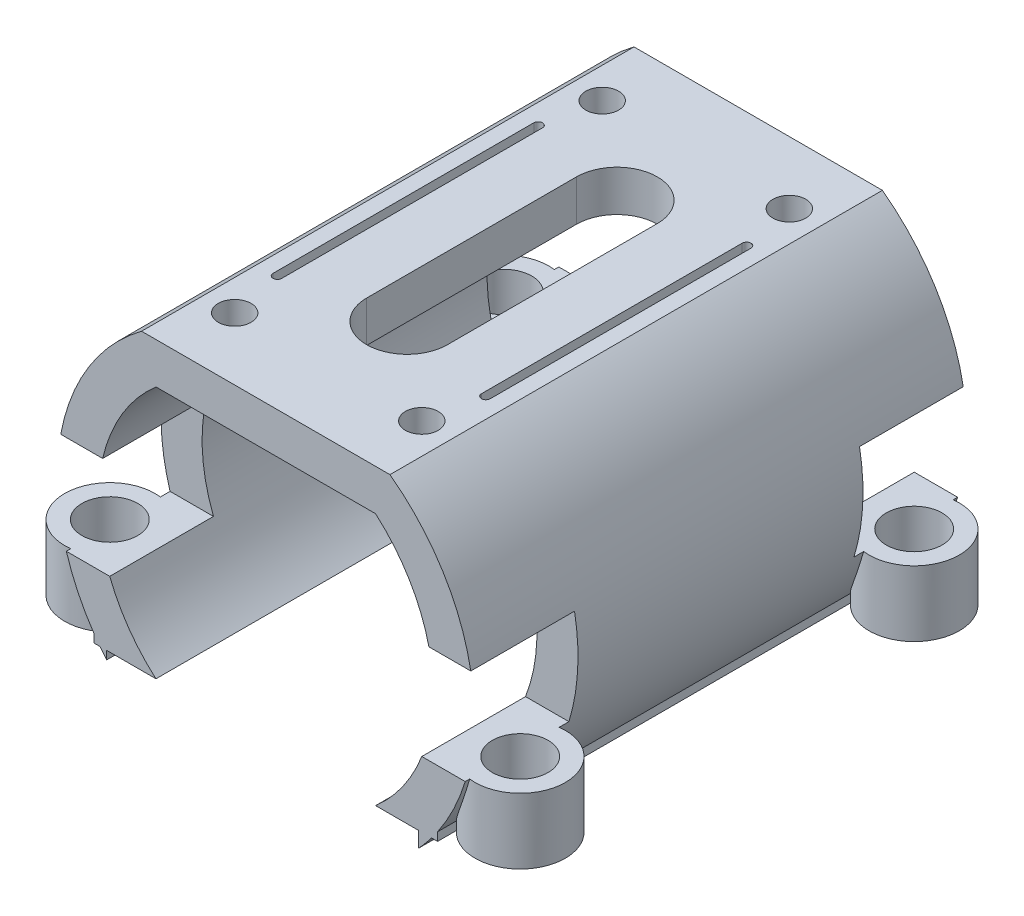
SolidWorks part; units mm, degrees
ref_plane "Alzado" through (0, 0, 0) normal (0, 0, 1) x (1, 0, 0)
ref_plane "Planta" through (0, 0, 0) normal (0, 1, 0) x (1, 0, 0)
ref_plane "Vista lateral" through (0, 0, 0) normal (1, 0, 0) x (0, 0, -1)
sketch "Croquis1" plane through (0, 0, 0) normal (0, 0, 1) x (1, 0, 0)
  line L0 (-6.6895, 7.7) -> (6.6895, 7.7)
  line L1 (-6.6895, -7.7) -> (6.6895, -7.7)
  arc A0 (-6.6895, 7.7) -> (-6.6895, -7.7) centre (0, 0) ccw
  arc A1 (6.6895, -7.7) -> (6.6895, 7.7) centre (0, 0) ccw
  dimension "D1" = 20.4
  dimension "D2" = 7.7
  dimension "D3" = 15.4
extrude "Saliente-Extruir1" add sketch "Croquis1" along normal blind 30
shell "Vaciado1" thickness 2.5 removed face at (0, 0, 30) outward yes
sketch "Croquis2" plane through (0, 0, -2.5) normal (0, 0, -1) x (-1, 0, 0)
  line L1 (-20.823, 15.7006) -> (20.823, 15.7006)
  line L2 (-20.823, 15.7006) -> (-20.823, -15.7006)
  line L3 (-20.823, -15.7006) -> (20.823, -15.7006)
  line L4 (20.823, 15.7006) -> (20.823, -15.7006)
  line L5 (-20.823, 15.7006) -> (20.823, -15.7006) construction
  line L6 (-20.823, -15.7006) -> (20.823, 15.7006) construction
  point P0 (0, 0)
extrude "Cortar-Extruir1" cut sketch "Croquis2" against normal blind 2.5
sketch "Croquis3" plane through (0, 0, 30) normal (0, 0, 1) x (1, 0, 0)
  line L1 (9.3098, -7.7) -> (-9.6926, -7.7)
  line L2 (9.3098, -7.7) -> (9.3098, -10.6722)
  line L3 (9.3098, -10.6722) -> (-9.6926, -10.6722)
  line L4 (-9.6926, -7.7) -> (-9.6926, -10.6722)
extrude "Cortar-Extruir2" cut sketch "Croquis3" against normal blind 48.3
sketch "Croquis4" plane through (0, -7.7, 0) normal (0, -1, 0) x (1, 0, 0)
  line L0 (0, 0) -> (0, 30) construction
  line L1 (6.6895, 30) -> (-6.6895, 30) construction
  line L2 (0, 15) -> (16.7401, 15) construction
  circle A0 centre (12.5, 3) radius 1.7
  circle A1 centre (12.5, 27) radius 1.7
  circle A2 centre (-12.5, 27) radius 1.7
  circle A3 centre (-12.5, 3) radius 1.7
  circle A4 centre (12.5, 3) radius 2.75
  circle A5 centre (12.5, 27) radius 2.75
  circle A6 centre (-12.5, 27) radius 2.75
  circle A7 centre (-12.5, 3) radius 2.75
  dimension "D3" = 3.4
  dimension "D4" = 5.5
  dimension "D1" = 12.5
  dimension "D2" = 12
extrude "Saliente-Extruir2" add sketch "Croquis4" against normal blind 4 separate body
sketch "Croquis5" plane through (0, -7.7, 0) normal (0, -1, 0) x (1, 0, 0)
  line L0 (-7.5664, 30) -> (-12.7, 30) construction
  line L1 (-8.4065, 0.1) -> (-10.4676, 0.1)
  line L2 (-8.4065, 0.1) -> (-8.4065, 30)
  line L3 (-8.4065, 30) -> (-10.4676, 30)
  line L4 (-10.4676, 0.1) -> (-10.4676, 30)
  line L5 (0, 0) -> (0, 12.3583) construction
  line L6 (10.4676, 0.1) -> (10.4676, 30)
  line L7 (8.4065, 30) -> (10.4676, 30)
  line L8 (8.4065, 0.1) -> (8.4065, 30)
  line L9 (8.4065, 0.1) -> (10.4676, 0.1)
extrude "Saliente-Extruir3" add sketch "Croquis5" against normal blind 1.5
sketch "Croquis6" plane through (0, 10.2, 0) normal (0, 1, 0) x (1, 0, 0)
  line L0 (0, 0) -> (0, -30) construction
  line L1 (7.5664, -30) -> (-7.5664, -30) construction
  line L2 (0, -30) -> (0, -15) construction
  line L3 (0, -15) -> (12.7, -15) construction
  line L4 (12.7, -30) -> (12.7, 0) construction
  line L5 (0, -21.3925) -> (0, -8.6075) construction
  line L6 (-2.4626, -21.3925) -> (-2.4626, -8.6075)
  line L7 (2.4626, -21.3925) -> (2.4626, -8.6075)
  line L8 (6.35, -7.0579) -> (6.35, -22.9421) construction
  line L9 (6.6165, -7.0579) -> (6.6165, -22.9421)
  line L10 (6.0835, -7.0579) -> (6.0835, -22.9421)
  line L11 (-6.35, -7.0579) -> (-6.35, -22.9421) construction
  line L12 (-6.6165, -7.0579) -> (-6.6165, -22.9421)
  line L13 (-6.0835, -7.0579) -> (-6.0835, -22.9421)
  arc A0 (-2.4626, -21.3925) -> (2.4626, -21.3925) centre (0, -21.3925) ccw
  arc A1 (2.4626, -8.6075) -> (-2.4626, -8.6075) centre (0, -8.6075) ccw
  arc A2 (6.6165, -7.0579) -> (6.0835, -7.0579) centre (6.35, -7.0579) ccw
  arc A3 (6.0835, -22.9421) -> (6.6165, -22.9421) centre (6.35, -22.9421) ccw
  circle A4 centre (5.7, -3.805) radius 1
  circle A5 centre (5.7, -26.195) radius 1
  arc A6 (-6.6165, -7.0579) -> (-6.0835, -7.0579) centre (-6.35, -7.0579) cw
  arc A7 (-6.0835, -22.9421) -> (-6.6165, -22.9421) centre (-6.35, -22.9421) cw
  circle A8 centre (-5.7, -3.805) radius 1
  circle A9 centre (-5.7, -26.195) radius 1
  point P11 (0, -15)
  point P17 (6.35, -15)
  point P29 (-6.35, -15)
  point P34 (0, -8.6075)
  dimension "D1" = 2
extrude "Cortar-Extruir3" cut sketch "Croquis6" against normal blind 7
sketch "Croquis9" plane through (0, 0, 0) normal (1, 0, 0) x (0, 0, -1)
  line L0 (-15, -7.7) -> (-15, 10.2) construction
  line L1 (-25.1474, -7.7) -> (-4.8526, -7.7) construction
  line L2 (-30, 10.2) -> (0, 10.2) construction
  line L3 (-30, -3.7) -> (0, -3.7) construction
  line L4 (1.4369, -3.7) -> (-6.3186, -3.7)
  line L5 (1.4369, -3.7) -> (1.4369, 2.3004)
  line L6 (1.4369, 2.3004) -> (-6.3186, 2.3004)
  line L7 (-6.3186, -3.7) -> (-6.3186, 2.3004)
  line L8 (-31.4369, 2.3004) -> (-23.6814, 2.3004)
  line L9 (-23.6814, -3.7) -> (-23.6814, 2.3004)
  line L10 (-31.4369, -3.7) -> (-23.6814, -3.7)
  line L11 (-31.4369, -3.7) -> (-31.4369, 2.3004)
extrude "Cortar-Extruir4" cut sketch "Croquis9" against normal blind 32 and the other way blind 30
sketch "Croquis10" plane through (0, -7.7, 0) normal (0, -1, 0) x (1, 0, 0)
  circle A0 centre (12.5, 27) radius 1.7
  circle A1 centre (-12.5, 27) radius 1.7
  circle A2 centre (12.5, 3) radius 1.7
  circle A3 centre (-12.5, 3) radius 1.7
extrude "Cortar-Extruir5" cut sketch "Croquis10" against normal blind 9
